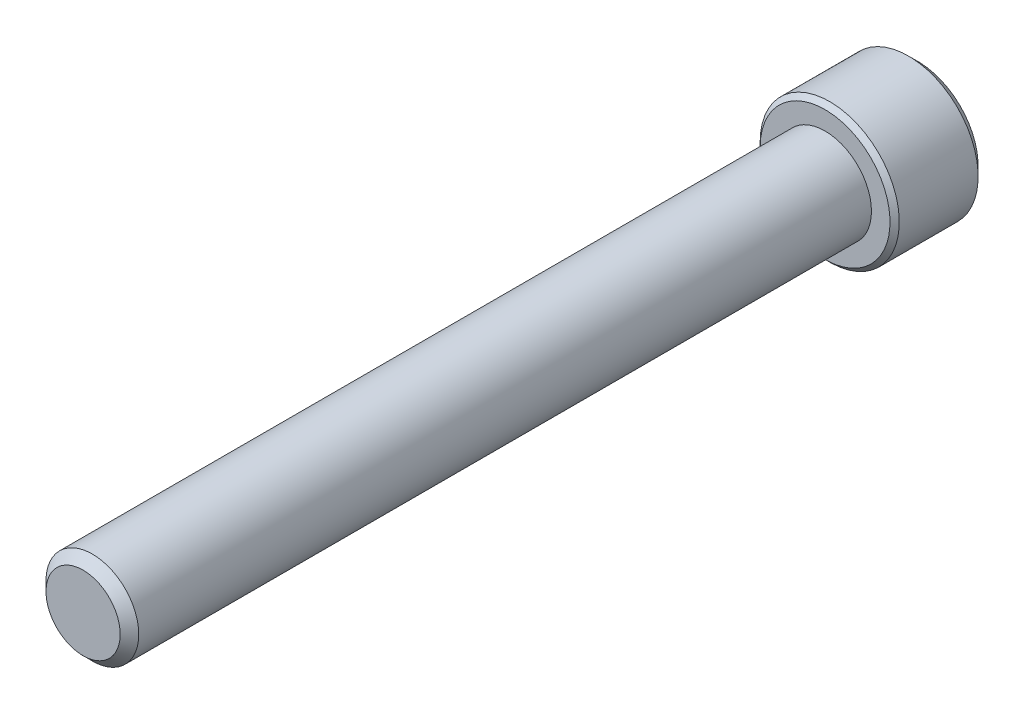
SolidWorks part; units mm, degrees
ref_plane "Front Plane" through (0, 0, 0) normal (0, 0, 1) x (1, 0, 0)
ref_plane "Top Plane" through (0, 0, 0) normal (0, 1, 0) x (1, 0, 0)
ref_plane "Right Plane" through (0, 0, 0) normal (1, 0, 0) x (0, 0, -1)
sketch "Sketch1" plane through (0, 0, 0) normal (0, 0, 1) x (1, 0, 0)
  line L0 (0, 3.9688) -> (0, -3.9688) construction
  circle A0 centre (0, 0) radius 3.9688
  dimension "OD" = 7.9375
extrude "Extrude1" add sketch "Sketch1" against normal blind 63.5
sketch "Sketch2" plane through (0, 0, 0) normal (0, 0, 1) x (1, 0, 0)
  circle A0 centre (0, 0) radius 3.9688 construction
  circle A1 centre (0, 0) radius 3.9688
curve "Helix/Spiral1" pitch 1.0583 height 30.6917 turns 29 parameters "pitch"=1.0583
chamfer "Chamfer3" distance 0.7937 angle 45 1 edges at (3.9688, 0, 0)
sketch "Sketch3" plane through (0, 0, 0) normal (1, 0, 0) x (0, 0, -1)
  line L0 (-0.926, 3.9688) -> (-0.5292, 3.2813)
  line L1 (-0.5292, 3.2813) -> (-0.3969, 3.2813)
  line L2 (-0.3969, 3.2813) -> (0, 3.9688)
  line L3 (-0.926, 3.9688) -> (0, 3.9688)
  line L4 (-0.463, 3.9688) -> (-0.463, 3.2813) construction
  line L5 (-0.7276, 3.625) -> (-0.1984, 3.625) construction
  line L6 (0, 3.9688) -> (0, -3.9688) construction
  dimension "D1" = 0.1323
  dimension "D2" = 0.5292
  dimension "D3" = 60
sweep "Cut-Sweep1" [suppressed] cut profiles "Sketch3" path "Helix/Spiral1"
sketch "Sketch5" plane through (0, 0, 0) normal (1, 0, 0) x (0, 0, -1)
  line L1 (63.5, 3.9688) -> (28.575, 3.9688)
  line L2 (63.5, 3.9688) -> (63.5, 0)
  line L3 (63.5, 0) -> (28.575, 0)
  line L4 (28.575, 3.9688) -> (28.575, 0) construction
  line L6 (0, 0) -> (9.9695, 0) construction
  line L8 (28.575, 3.9688) -> (24.6062, 0)
  line L9 (24.6062, 0) -> (28.575, 0)
  line L10 (63.5, -3.9688) -> (63.5, 3.9688) construction
  dimension "D1" = 45
  dimension "Thread min" = 28.575
revolve "partially thread" add sketch "Sketch5" angle 360 about L6
sketch "Sketch6" plane through (0, 0, -63.5) normal (0, 0, -1) x (-1, 0, 0)
  circle A0 centre (0, 0) radius 5.9531
  dimension "head dia" = 11.9062
extrude "Extrude2" add sketch "Sketch6" along normal blind 7.9375
sketch "Sketch7" plane through (0, 0, -71.4375) normal (0, 0, -1) x (-1, 0, 0)
  line L1 (0, 3.6662) -> (-3.175, 1.8331)
  line L2 (-3.175, 1.8331) -> (-3.175, -1.8331)
  line L3 (-3.175, -1.8331) -> (0, -3.6662)
  line L4 (0, -3.6662) -> (3.175, -1.8331)
  line L5 (3.175, -1.8331) -> (3.175, 1.8331)
  line L6 (3.175, 1.8331) -> (0, 3.6662)
  circle A0 centre (0, 0) radius 3.175 construction
  dimension "hex dia" = 6.35
extrude "Cut-Extrude1" cut sketch "Sketch7" against normal blind 4.7625
sketch "Sketch8" plane through (0, 0, -71.4375) normal (0, 0, -1) x (-1, 0, 0)
  circle A0 centre (0, 0) radius 3.6662
extrude "Cut-Extrude2" cut sketch "Sketch8" against normal blind 0.7937 draft 45
chamfer "Chamfer1" distance 0.7937 angle 45 1 edges at (-5.9531, 0, -71.4375)
chamfer "Chamfer2" distance 0.3969 angle 45 1 edges at (-5.9531, 0, -63.5)
sketch "Sketch9" plane through (0, 0, 0) normal (1, 0, 0) x (0, 0, -1)
  line L0 (0, 3.9688) -> (0, -3.9688) construction
  line L1 (5.8208, 3.9688) -> (5.8208, -3.9688) construction
  line L2 (63.5, 5.9531) -> (63.5, -5.9531) construction
  line L3 (71.4375, 5.9531) -> (71.4375, -5.9531) construction
  line L4 (71.4375, 0) -> (0, 0) construction
  line L5 (61.6852, 3.9688) -> (61.6852, -3.9688) construction
  dimension "D1" = 5.8208
  dimension "D2" = 7.9375
  dimension "D3" = 11.9062
  dimension "D4" = 63.5
  dimension "Thread Length" = 61.6852
equation "\"D3@Helix/Spiral1\" = \"Thread min@Sketch5\"+(\"pitch@Helix/Spiral1\"*2)"
equation "\"D1@Sketch3\" = \"pitch@Helix/Spiral1\"*.125"
equation "\"D2@Sketch3\" = \"pitch@Helix/Spiral1\"*.5"
equation "\"D1@Cut-Extrude1\" = \"hex dia@Sketch7\"*.75"
equation "\"D1@Chamfer1\" = \"head depth@Extrude2\"/10"
equation "\"D1@Sketch9\" = \"pitch@Helix/Spiral1\"*5.5"
equation "\"D1@Chamfer2\" = \"D1@Chamfer1\"/2"
equation "\"D1@Cut-Extrude2\" = \"D1@Chamfer2\"*2"
equation "\"D1@Chamfer3\" = \"pitch@Helix/Spiral1\"*.750"
equation "\"D2@Sketch9\" = \"head depth@Extrude2\""
equation "\"D3@Sketch9\" = \"head dia@Sketch6\""
equation "\"D4@Sketch9\" = \"screw length@Extrude1\""
